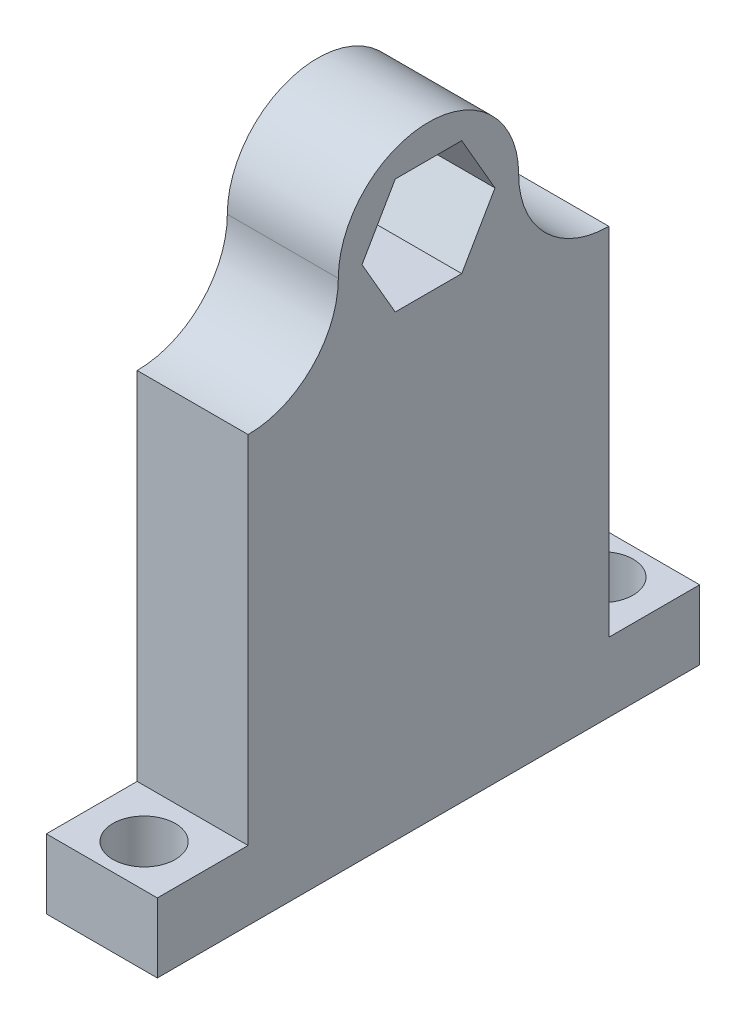
SolidWorks part; units mm, degrees
ref_plane "Спереди" through (0, 0, 0) normal (0, 0, 1) x (1, 0, 0)
ref_plane "Сверху" through (0, 0, 0) normal (0, 1, 0) x (1, 0, 0)
ref_plane "Справа" through (0, 0, 0) normal (1, 0, 0) x (0, 0, -1)
sketch "Эскиз1" plane through (0, 0, 0) normal (1, 0, 0) x (0, 0, -1)
  line L6 (-6.5, 0) -> (6.5, 0) construction
  line L12 (-13, -6.5) -> (-13, -11.5)
  line L13 (13, -6.5) -> (13, -11.5)
  line L15 (-13, -11.5) -> (13, -11.5)
  arc A0 (6.5, 0) -> (-6.5, 0) centre (0, 0) ccw
  arc A1 (-13, -6.5) -> (-6.5, 0) centre (-13, 0) ccw
  arc A2 (6.5, 0) -> (13, -6.5) centre (13, 0) ccw
  point P4 (0, 0)
  point P7 (0, -39.795)
  point P9 (0, 6.5)
  dimension "D1" = 13
  dimension "D4" = 13
  dimension "D5" = 13
  dimension "D2" = 5
extrude "Бобышка-Вытянуть1" add sketch "Эскиз1" along normal blind 8
sketch "Эскиз2" plane through (8, 0, 0) normal (1, 0, 0) x (0, 0, -1)
  line L1 (4.792, 0) -> (2.396, 4.15)
  line L2 (2.396, 4.15) -> (-2.396, 4.15)
  line L3 (-2.396, 4.15) -> (-4.792, 0)
  line L4 (-4.792, 0) -> (-2.396, -4.15)
  line L5 (-2.396, -4.15) -> (2.396, -4.15)
  line L6 (2.396, -4.15) -> (4.792, 0)
  circle A0 centre (0, 0) radius 4.15 construction
  dimension "D1" = 8.3
extrude "Вырез-Вытянуть1" cut sketch "Эскиз2" against normal through all
sketch "Эскиз4" plane through (0, -11.5, 0) normal (0, -1, 0) x (1, 0, 0)
  line L8 (0, 13) -> (0, -13)
  line L9 (0, -13) -> (8, -13)
  line L10 (8, -13) -> (8, 13)
  line L11 (8, 13) -> (0, 13)
  line L12 (0, 13) -> (0, -13)
  line L13 (0, -13) -> (8, -13)
  line L14 (8, -13) -> (8, 13)
  line L15 (8, 13) -> (0, 13)
  dimension "D1" = 0
extrude "Бобышка-Вытянуть2" add sketch "Эскиз4" along normal up to surface (25.65 mm away)
sketch "Эскиз5" plane through (0, -37.15, 0) normal (0, -1, 0) x (1, 0, 0)
  line L0 (0, 13) -> (0, -13) construction
  line L1 (0, 19.5455) -> (8, 19.5455)
  line L2 (0, 19.5455) -> (0, -19.5455)
  line L3 (0, -19.5455) -> (8, -19.5455)
  line L4 (8, 19.5455) -> (8, -19.5455)
  line L5 (8, -13) -> (8, 13) construction
  line L6 (534, -19.5455) -> (-6, -19.5455) construction
  line L7 (534, 19.5455) -> (-6, 19.5455) construction
  line L8 (4, -16.5) -> (4, 16.5) construction
  line L9 (8, -19.5455) -> (0, 19.5455) construction
  line L10 (0, -19.5455) -> (8, 19.5455) construction
  circle A0 centre (4, -16.5) radius 2.25
  circle A1 centre (4, 16.5) radius 2.25
  point P16 (4, 0)
  point P17 (8, 0)
  point P18 (4, 0)
  dimension "D1" = 4.5
  dimension "D2" = 4.5
  dimension "D3" = 33
extrude "Бобышка-Вытянуть3" add sketch "Эскиз5" against normal blind 5
